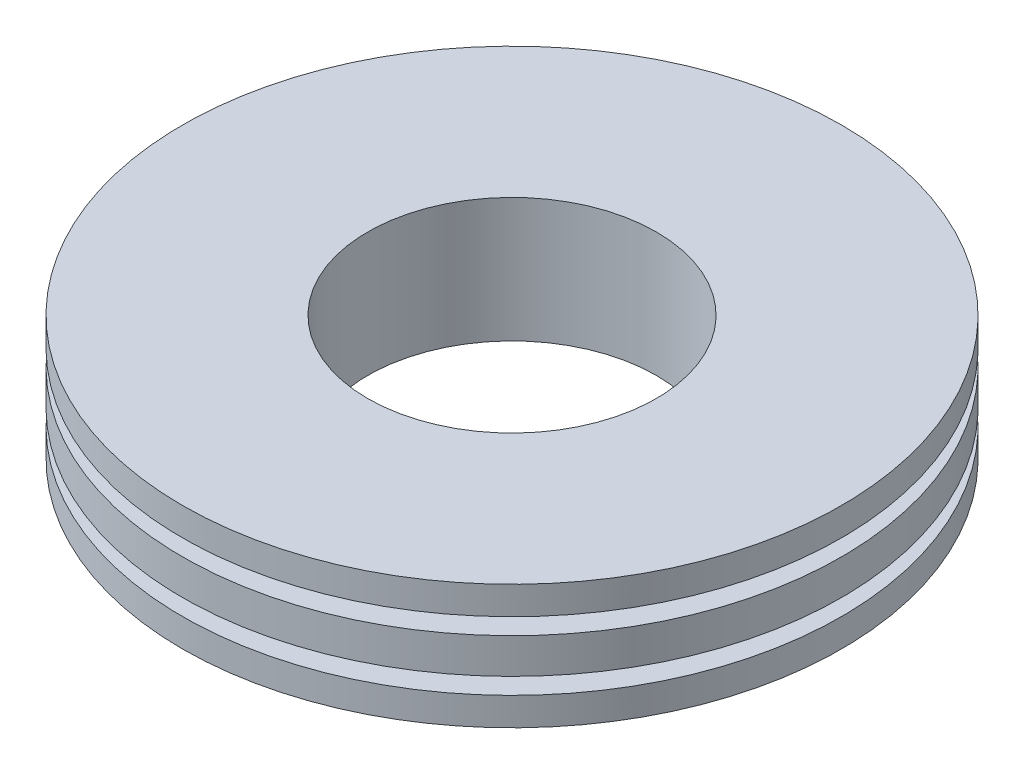
SolidWorks part; units mm, degrees
material "Chrome Stainless Steel"
ref_plane "Front Plane" through (0, 0, 0) normal (0, 0, 1) x (1, 0, 0)
ref_plane "Top Plane" through (0, 0, 0) normal (0, 1, 0) x (1, 0, 0)
ref_plane "Right Plane" through (0, 0, 0) normal (1, 0, 0) x (0, 0, -1)
sketch "Sketch1" plane through (0, 0, 0) normal (0, 1, 0) x (1, 0, 0)
  circle A0 centre (0, 0) radius 9.385
  circle A1 centre (0, 0) radius 4.11
  dimension "D1" = 18.77
  dimension "D2" = 8.22
extrude "Boss-Extrude1" add sketch "Sketch1" along normal blind 3.54
sketch "Sketch2" plane through (0, 0, 0) normal (0, 0, 1) x (1, 0, 0)
  line L0 (9.385, 0.8) -> (7.6101, 0.8)
  line L1 (9.385, 0) -> (9.385, 3.54) construction
  line L2 (7.6101, 0.8) -> (7.6101, 1.2677)
  line L3 (7.6101, 1.2677) -> (9.385, 1.2677)
  line L4 (-9.385, 0) -> (9.385, 0) construction
  line L5 (-9.385, 1.77) -> (9.385, 1.77) construction
  line L6 (-9.385, 3.54) -> (-9.385, 0) construction
  line L7 (9.385, 1.2677) -> (9.385, 0.8)
  line L8 (0, 0) -> (0, 6.2978) construction
  line L9 (9.385, 2.2723) -> (9.385, 2.74)
  line L10 (9.385, 2.74) -> (7.6101, 2.74)
  line L11 (7.6101, 2.74) -> (7.6101, 2.2723)
  line L12 (7.6101, 2.2723) -> (9.385, 2.2723)
  dimension "D1" = 0.8
revolve "Cut-Revolve1" cut sketch "Sketch2" angle 360 about L8
ref_axis "Axis1" through (0, 3.717, 0) along (0, -1, 0)
